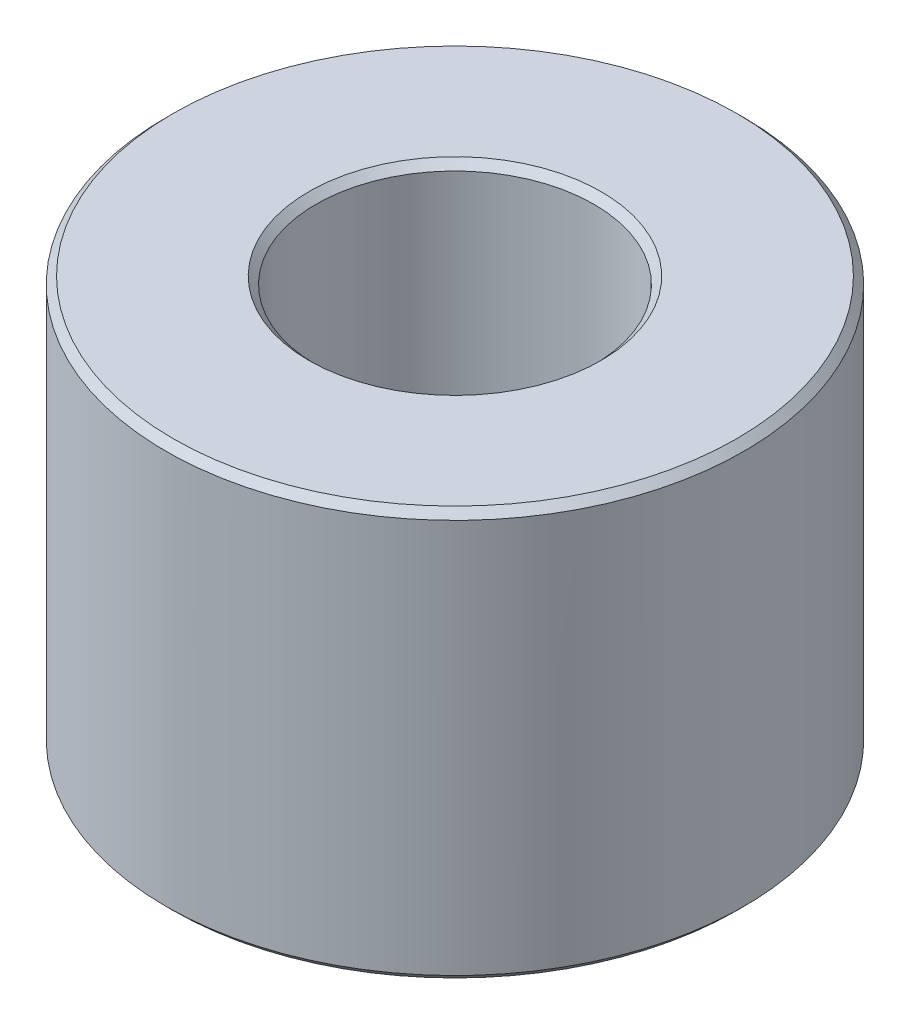
SolidWorks part; units mm, degrees
ref_plane "Front Plane" through (0, 0, 0) normal (0, 0, 1) x (1, 0, 0)
ref_plane "Top Plane" through (0, 0, 0) normal (0, 1, 0) x (1, 0, 0)
ref_plane "Right Plane" through (0, 0, 0) normal (1, 0, 0) x (0, 0, -1)
sketch "Sketch1" plane through (0, 0, 0) normal (0, 1, 0) x (1, 0, 0)
  circle A0 centre (0, 0) radius 55
  dimension "SLEEVE_OD" = 110
extrude "Boss-Extrude1" add sketch "Sketch1" along normal blind 77.772
sketch "Sketch2" plane through (0, 0, 0) normal (0, 1, 0) x (1, 0, 0)
  circle A0 centre (0, 0) radius 26.4434
  dimension "BORE_D" = 52.8868
extrude "Cut-Extrude1" cut sketch "Sketch2" along normal through all
chamfer "Chamfer1" distance 1.3821 angle 45 4 edges at (0, 77.772, 26.4434) (0, 0, 26.4434) (0, 0, 55) (0, 77.772, 55)
